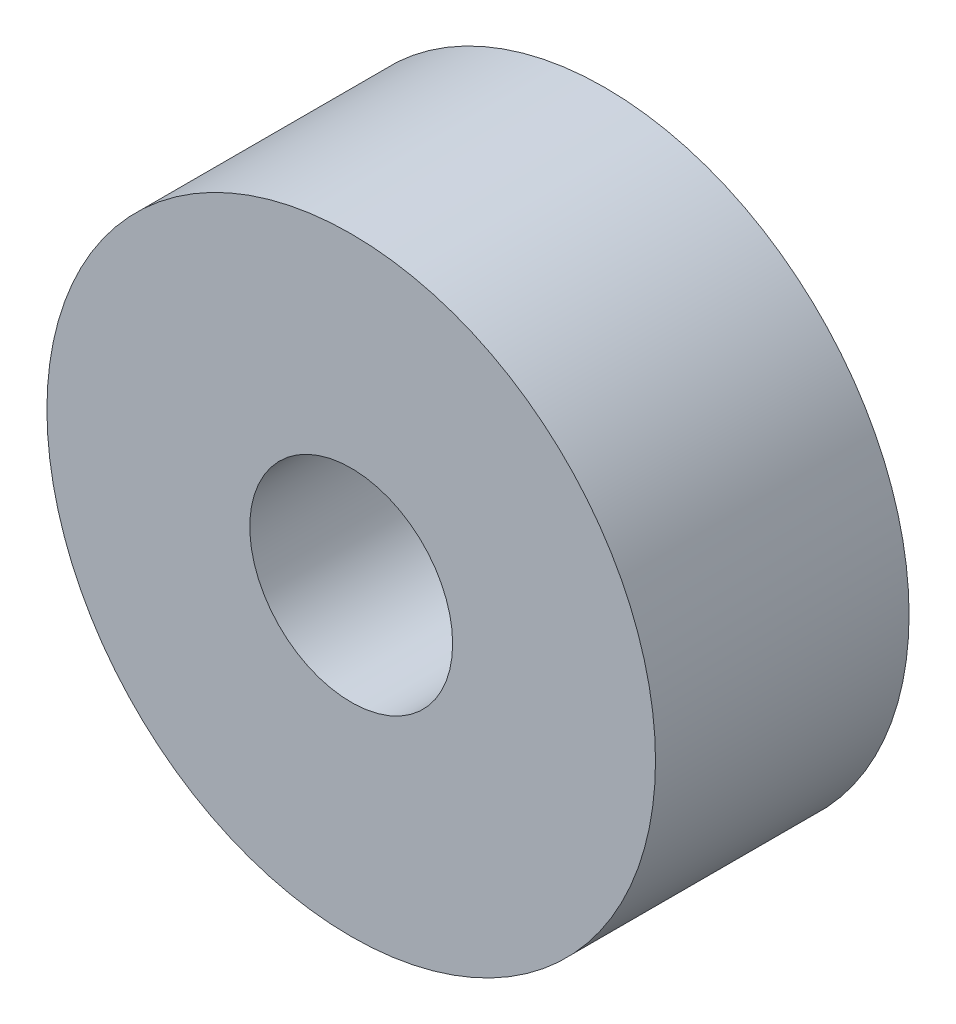
SolidWorks part; units mm, degrees
material "Delrin 2700 NC010, Low Viscosity Acetal Copolymer (SS)"
ref_plane "Front Plane" through (0, 0, 0) normal (0, 0, 1) x (1, 0, 0)
ref_plane "Top Plane" through (0, 0, 0) normal (0, 1, 0) x (1, 0, 0)
ref_plane "Right Plane" through (0, 0, 0) normal (1, 0, 0) x (0, 0, -1)
sketch "Sketch1" plane through (0, 0, 0) normal (0, 0, 1) x (1, 0, 0)
  circle A0 centre (0, 0) radius 9.525
  circle A1 centre (0, 0) radius 3.175
  dimension "D1" = 19.05
  dimension "D2" = 6.35
extrude "Boss-Extrude1" add sketch "Sketch1" along normal blind 7.9375
hole_wizard "Tap Drill for #6-32 Tap1" positions "Sketch4" profile "Sketch2" hole size "#6-32" standard "ANSI Inch"
sketch "Sketch4" plane through (0, 0, 0) normal (0, 0, -1) x (-1, 0, 0)
  circle A0 centre (0, 0) radius 3.175 construction
  point P0 (6.35, 0)
  point P2 (-6.35, 0)
  dimension "D1" = 6.35
  dimension "D2" = 6.35
sketch "Sketch2" plane through (-6.35, 0, 0) normal (1, 0, 0) x (0, 1, 0)
  line L0 (0, 0) -> (0, 7.1627)
  line L1 (0, 7.1627) -> (1.3525, 6.35)
  line L2 (1.3525, 6.35) -> (1.3525, 0)
  line L5 (1.3525, 0) -> (0, 0)
  line L10 (0, 7.1627) -> (-1.3526, 6.35) construction
  line L11 (0, -6.35) -> (0, 107.95) construction
  dimension "Hole Dia." = 2.7051
  dimension "Hole Depth" = 6.35
  dimension "Drill Angle" = 118
hole_wizard "1/8 (0.125) Diameter Hole1" positions "Sketch6" profile "Sketch5" hole size "1/8" standard "ANSI Inch"
sketch "Sketch6" plane through (0, 0, 0) normal (0, 0, -1) x (-1, 0, 0)
  circle A0 centre (0, 0) radius 3.175 construction
  point P0 (0, -6.35)
  point P2 (0, 6.35)
  dimension "D1" = 6.35
  dimension "D2" = 6.35
sketch "Sketch5" plane through (0, -6.35, 0) normal (1, 0, 0) x (0, 1, 0)
  line L0 (0, 0) -> (0, 7.3039)
  line L1 (0, 7.3039) -> (1.5875, 6.35)
  line L2 (1.5875, 6.35) -> (1.5875, 0)
  line L5 (1.5875, 0) -> (0, 0)
  line L10 (0, 7.3039) -> (-1.5875, 6.35) construction
  line L11 (0, -6.35) -> (0, 107.95) construction
  dimension "Hole Dia." = 3.175
  dimension "Hole Depth" = 6.35
  dimension "Drill Angle" = 118
